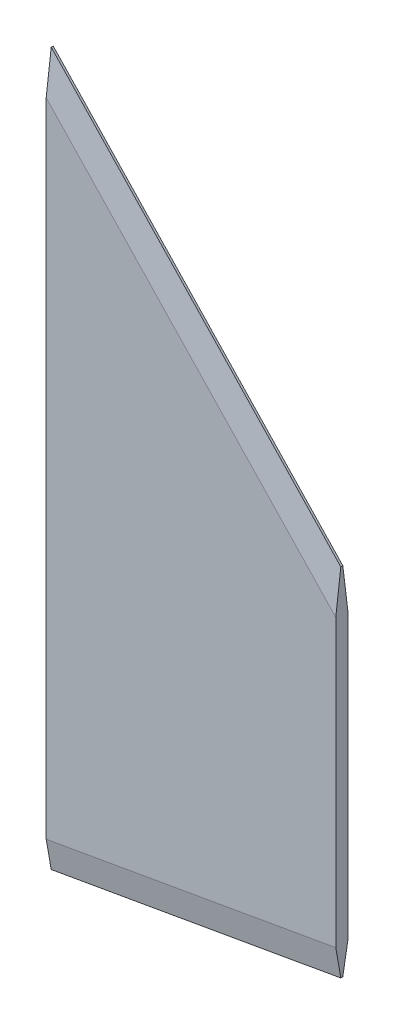
SolidWorks part; units mm, degrees
material "Hexcel AS4C (3000 Filaments)"
ref_plane "Front Plane" through (0, 0, 0) normal (0, 0, 1) x (1, 0, 0)
ref_plane "Top Plane" through (0, 0, 0) normal (0, 1, 0) x (1, 0, 0)
ref_plane "Right Plane" through (0, 0, 0) normal (1, 0, 0) x (0, 0, -1)
sketch "Sketch1" plane through (0, 0, 0) normal (0, 0, 1) x (1, 0, 0)
  line L0 (-60.9816, 96.1508) -> (-60.9816, -81.6492)
  line L1 (-60.9816, -81.6492) -> (11.3132, -68.9492)
  line L2 (11.3132, -68.9492) -> (11.3132, 19.9508)
  line L3 (11.3132, 19.9508) -> (-60.9816, 96.1508)
  point P5 (21.5684, -68.9492)
  point P6 (0, 0)
  point P8 (0, 0)
  point P9 (-60.9816, -81.6492)
  point P11 (-60.9816, 96.1508)
  point P13 (21.5684, 19.9508)
extrude "Boss-Extrude1" add sketch "Sketch1" along normal mid plane 3
chamfer "Chamfer1" distance 1.25 angle 80 4 edges at (-24.8342, -75.2992, -1.5) (-24.8342, -75.2992, 1.5) (-24.8342, 58.0508, -1.5) (-24.8342, 58.0508, 1.5) first distance on face at (-24.8342, -75.2992, 0) first distance on face at (-24.8342, 58.0508, 0)
